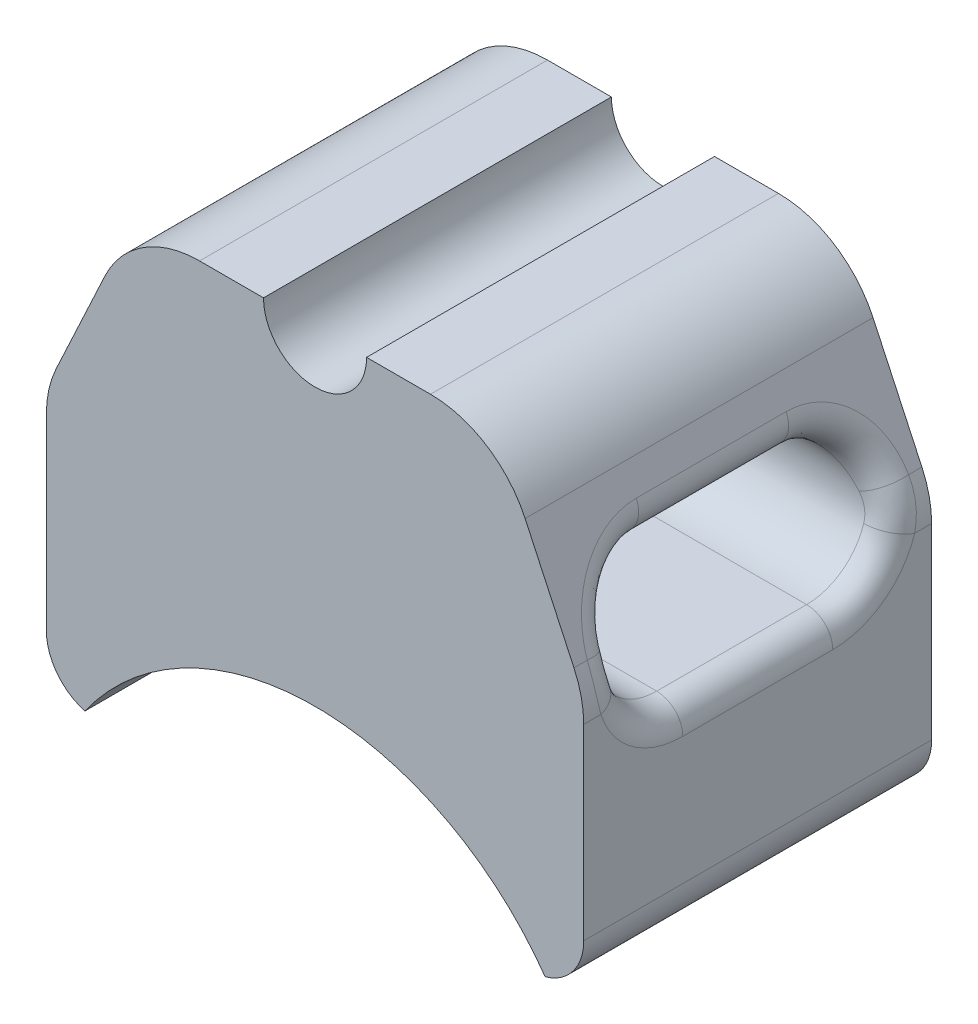
SolidWorks part; units mm, degrees
ref_plane "Front Plane" through (0, 0, 0) normal (0, 0, 1) x (1, 0, 0)
ref_plane "Top Plane" through (0, 0, 0) normal (0, 1, 0) x (1, 0, 0)
ref_plane "Right Plane" through (0, 0, 0) normal (1, 0, 0) x (0, 0, -1)
sketch "Sketch1" plane through (0, 0, 0) normal (0, 0, 1) x (1, 0, 0)
  line L0 (0, 0) -> (0, 12.7)
  line L1 (4.219, 21.761) -> (10.569, 21.761)
  line L5 (15.5855, 21.761) -> (21.9355, 21.761)
  line L6 (24.2764, 0) -> (26.1546, 0)
  line L7 (26.1546, 0) -> (26.1546, 12.7)
  line L8 (0, 0) -> (1.8782, 0)
  line L9 (21.9355, 21.761) -> (26.1546, 12.7)
  line L10 (4.219, 21.761) -> (0, 12.7)
  line L11 (10.569, 21.761) -> (15.5855, 21.761) construction
  arc A5 (10.569, 21.761) -> (15.5855, 21.761) centre (13.0773, 21.761) ccw
  arc A7 (1.8782, 0) -> (24.2764, 0) centre (13.0773, -7.9189) cw
  dimension "D1" = 12.7
  dimension "D2" = 2.5082
  dimension "D3" = 13.716
  dimension "D4" = 1.8782
  dimension "D5" = 6.35
  dimension "D6" = 9.061
  dimension "D7" = 7.9189
extrude "Boss-Extrude2" add sketch "Sketch1" along normal blind 16.9342 contours L6 L7 L9 L5 A5 L1 L10 L0 L8 A7
fillet "Fillet1" radius 5.08 4 edges at (0, 12.7, 8.4671) (4.219, 21.761, 8.4671) (26.1546, 12.7, 8.4671) (21.9355, 21.761, 8.4671)
fillet "Fillet2" radius 2.54 2 edges at (0, 0, 8.4671) (26.1546, 0, 8.4671)
ref_plane "Plane1" through (28.6946, 0, 0) normal (1, 0, 0) x (0, 0, -1)
sketch "Sketch6" plane through (28.6946, 0, 0) normal (1, 0, 0) x (0, 0, -1)
  line L0 (-4.8144, 12.8453) -> (-12.1121, 12.8453) construction
  line L1 (-4.8144, 9.9301) -> (-12.1121, 9.9301)
  line L2 (-4.8144, 15.7605) -> (-12.1121, 15.7605)
  line L3 (-16.9342, 18.8254) -> (-16.9342, 13.7196) construction
  line L4 (0, 11.5753) -> (-16.9342, 11.5753) construction
  arc A0 (-4.8144, 9.9301) -> (-4.8144, 15.7605) centre (-4.8144, 12.8453) ccw
  arc A1 (-12.1121, 15.7605) -> (-12.1121, 9.9301) centre (-12.1121, 12.8453) ccw
  point P2 (-8.4633, 12.8453)
  dimension "D1" = 8.4709
  dimension "D2" = 1.27
extrude "Cut-Extrude3" cut sketch "Sketch6" against normal through all both and the other way through all
fillet "Fillet3" radius 1.27 8 edges at (24.9926, 15.1955, 3.0896) (24.9926, 15.1955, 13.8369) (24.7295, 15.7605, 8.4633) (26.086, 12.4072, 1.9323) (26.1546, 10.3754, 3.2658) (26.1546, 9.9301, 8.4633) (26.1546, 10.3754, 13.6607) (25.989, 12.8618, 15.0273)
fillet "Fillet4" radius 1.27 8 edges at (1.162, 15.1955, 3.0896) (1.162, 15.1955, 13.8369) (1.425, 15.7605, 8.4633) (0.1656, 12.8618, 1.8992) (0, 10.3754, 3.2658) (0, 9.9301, 8.4633) (0, 10.3754, 13.6607) (0.0686, 12.4072, 14.9943)
